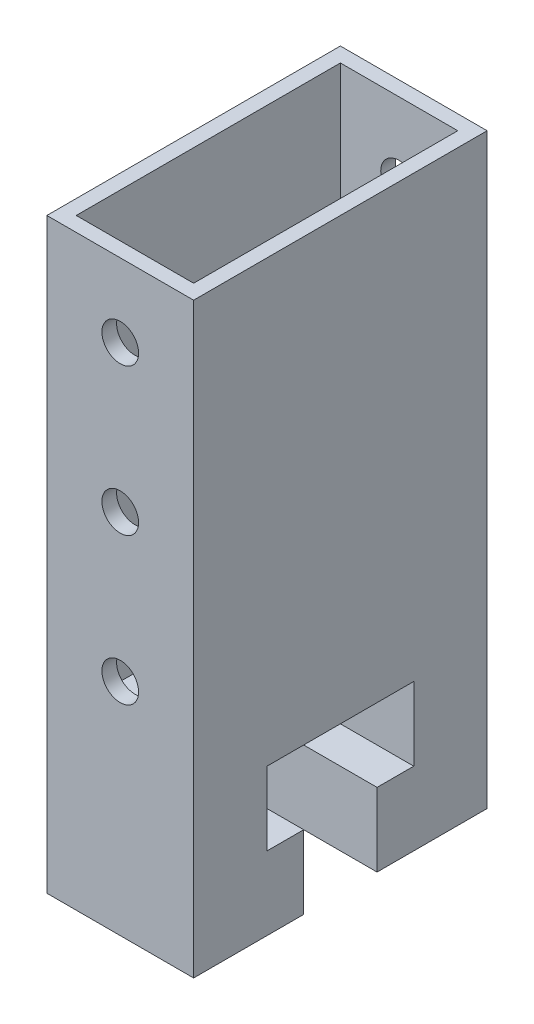
SolidWorks part; units mm, degrees
ref_plane "Front Plane" through (0, 0, 0) normal (0, 0, 1) x (1, 0, 0)
ref_plane "Top Plane" through (0, 0, 0) normal (0, 1, 0) x (1, 0, 0)
ref_plane "Right Plane" through (0, 0, 0) normal (1, 0, 0) x (0, 0, -1)
sketch "Sketch1" plane through (0, 0, 0) normal (0, 0, 1) x (1, 0, 0)
  line L1 (0, 0) -> (25.4, 0)
  line L2 (0, 0) -> (0, 101.6)
  line L3 (0, 101.6) -> (25.4, 101.6)
  line L4 (25.4, 0) -> (25.4, 101.6)
  dimension "D1" = 101.6
  dimension "D2" = 25.4
extrude "Boss-Extrude1" add sketch "Sketch1" along normal mid plane 50.8
sketch "Sketch2" plane through (0, 0, 25.4) normal (0, 0, 1) x (1, 0, 0)
  circle A1 centre (12.7, 38.1) radius 3.175
  circle A2 centre (12.7, 63.5) radius 3.175
  circle A3 centre (12.7, 88.9) radius 3.175
  dimension "D2" = 6.35
  dimension "D3" = 6.35
  dimension "D4" = 6.35
  dimension "D7" = 25.4
  dimension "D8" = 25.4
extrude "Cut-Extrude1" cut sketch "Sketch2" against normal through all
sketch "Sketch3" plane through (0, 101.6, 0) normal (0, 1, 0) x (1, 0, 0)
  line L0 (0, -25.4) -> (0, 25.4) construction
  line L1 (2.54, -22.86) -> (22.86, -22.86)
  line L2 (2.54, -22.86) -> (2.54, 22.86)
  line L3 (2.54, 22.86) -> (22.86, 22.86)
  line L4 (22.86, -22.86) -> (22.86, 22.86)
  line L5 (25.4, -25.4) -> (0, -25.4) construction
  dimension "D1" = 20.32
  dimension "D2" = 45.72
  dimension "D3" = 2.54
  dimension "D4" = 2.54
extrude "Cut-Extrude2" cut sketch "Sketch3" against normal blind 73.66
sketch "Sketch4" plane through (25.4, 0, 0) normal (1, 0, 0) x (0, 0, -1)
  line L0 (-6.35, 0) -> (-6.35, 12.7)
  line L1 (-25.4, 0) -> (25.4, 0) construction
  line L2 (-6.35, 12.7) -> (-12.7, 12.7)
  line L3 (-12.7, 12.7) -> (-12.7, 25.4)
  line L4 (-12.7, 25.4) -> (12.7, 25.4)
  line L5 (12.7, 25.4) -> (12.7, 12.7)
  line L6 (12.7, 12.7) -> (6.35, 12.7)
  line L7 (6.35, 12.7) -> (6.35, 0)
  line L8 (6.35, 0) -> (-6.35, 0)
  line L9 (-25.4, 0) -> (-25.4, 101.6) construction
  dimension "D1" = 12.7
  dimension "D2" = 12.7
  dimension "D3" = 12.7
  dimension "D4" = 6.35
  dimension "D5" = 12.7
  dimension "D6" = 6.35
  dimension "D7" = 19.05
extrude "Cut-Extrude3" cut sketch "Sketch4" against normal through all
